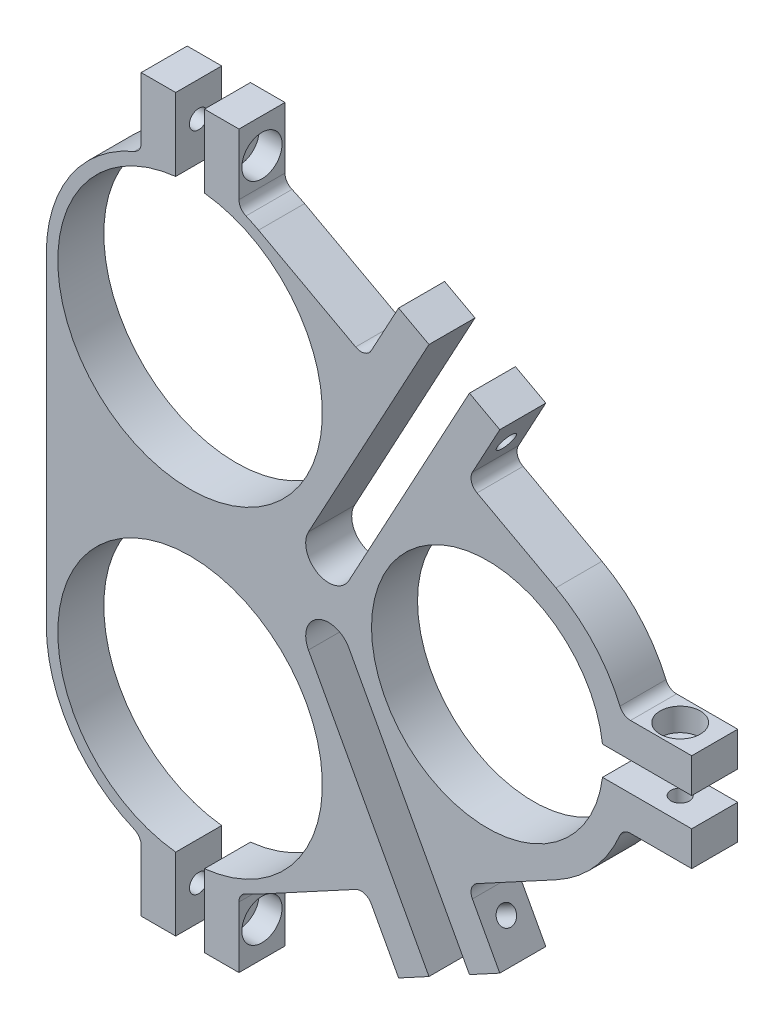
SolidWorks part; units mm, degrees
ref_plane "Front Plane" through (0, 0, 0) normal (0, 0, 1) x (1, 0, 0)
ref_plane "Top Plane" through (0, 0, 0) normal (0, 1, 0) x (1, 0, 0)
ref_plane "Right Plane" through (0, 0, 0) normal (1, 0, 0) x (0, 0, -1)
sketch "Sketch1" plane through (0, 0, 0) normal (0, 0, 1) x (1, 0, 0)
  line L0 (-39.6875, 88.9) -> (-39.6875, 0)
  line L1 (-39.6875, 44.45) -> (82.0822, 44.45) construction
  line L2 (18.8988, 123.7989) -> (48.4931, 107.7727)
  line L3 (3.9688, -36.2962) -> (3.9688, -56.3731)
  line L4 (0, 88.9) -> (0, 0) construction
  line L5 (-13.4938, -37.3231) -> (-13.4938, -56.3731)
  line L6 (3.9688, -56.3731) -> (13.4938, -56.3731)
  line L7 (-3.9688, -56.3731) -> (-13.4938, -56.3731)
  line L8 (13.4938, -37.3231) -> (13.4938, -56.3731)
  line L9 (-3.9687, -36.2962) -> (-3.9688, -56.3731)
  line L10 (18.8988, -34.8989) -> (48.4931, -18.8727)
  line L11 (13.4938, 126.2231) -> (13.4938, 145.2731)
  line L12 (-3.9688, 145.2731) -> (-13.4938, 145.2731)
  line L13 (3.9688, 145.2731) -> (13.4938, 145.2731)
  line L14 (3.9688, 145.2731) -> (3.9688, 125.1962)
  line L15 (-13.4938, 126.2231) -> (-13.4938, 145.2731)
  line L16 (56.8688, 103.237) -> (68.0364, 97.1894) construction
  line L17 (56.8688, 103.237) -> (32.6783, 58.5664)
  line L18 (-3.9688, 145.2731) -> (-3.9688, 125.1962)
  line L19 (68.0364, 97.1894) -> (43.846, 52.5188)
  line L20 (32.6783, 58.5664) -> (43.846, 52.5188) construction
  line L21 (56.8688, -14.337) -> (32.6783, 30.3336)
  line L22 (56.8688, 103.237) -> (65.9402, 119.9885)
  line L23 (3.9688, 145.2731) -> (-3.9688, 145.2731) construction
  line L24 (48.4931, 107.7727) -> (57.5645, 124.5242)
  line L25 (3.9688, -56.3731) -> (-3.9688, -56.3731) construction
  line L26 (65.9402, 119.9885) -> (57.5645, 124.5242)
  line L27 (38.2622, 55.5426) -> (62.4526, 100.2132) construction
  line L28 (68.0364, 97.1894) -> (77.1079, 113.9408)
  line L29 (77.1079, 113.9408) -> (85.4836, 109.4051)
  line L30 (76.4122, 92.6537) -> (85.4836, 109.4051)
  line L31 (76.4122, 92.6537) -> (100.981, 79.3489)
  line L32 (68.0364, -8.2894) -> (43.846, 36.3812)
  line L33 (76.4122, -3.7537) -> (85.4836, -20.5051)
  line L34 (77.1079, -25.0408) -> (85.4836, -20.5051)
  line L35 (68.0364, -8.2894) -> (77.1079, -25.0408)
  line L36 (56.8688, -14.337) -> (65.9402, -31.0885)
  line L37 (65.9402, -31.0885) -> (57.5645, -35.6242)
  line L38 (48.4931, -18.8727) -> (57.5645, -35.6242)
  line L39 (38.2622, 33.3574) -> (62.4526, -11.3132) construction
  line L40 (56.8688, -14.337) -> (68.0364, -8.2894) construction
  line L41 (76.4122, -3.7537) -> (100.981, 9.5511)
  line L42 (113.8392, 48.4187) -> (138.4553, 48.4187)
  line L43 (138.4553, 48.4187) -> (138.4553, 57.9437)
  line L44 (138.4553, 57.9437) -> (119.4053, 57.9437)
  line L45 (113.8392, 40.4812) -> (138.4553, 40.4812)
  line L46 (138.4553, 40.4812) -> (138.4553, 30.9563)
  line L47 (138.4553, 30.9563) -> (119.4053, 30.9562)
  arc A0 (3.9688, -36.2962) -> (-3.9687, -36.2962) centre (0, 0) ccw
  arc A1 (-3.9688, 125.1962) -> (3.9688, 125.1962) centre (0, 88.9) ccw
  arc A2 (13.4938, 126.2231) -> (18.8988, 123.7989) centre (0, 88.9) cw
  arc A3 (-39.6875, 0) -> (-13.4938, -37.3231) centre (0, 0) ccw
  arc A4 (113.8392, 48.4187) -> (113.8392, 40.4812) centre (82.0822, 44.45) ccw
  arc A5 (13.4938, -37.3231) -> (18.8988, -34.8989) centre (0, 0) ccw
  arc A6 (-39.6875, 88.9) -> (-13.4938, 126.2231) centre (0, 88.9) cw
  arc A7 (119.4053, 57.9437) -> (119.4053, 30.9562) centre (82.0822, 44.45) ccw construction
  circle A8 centre (0, 0) radius 36.5125 construction
  circle A9 centre (0, 88.9) radius 36.5125 construction
  circle A10 centre (0, 0) radius 39.6875 construction
  circle A11 centre (82.0822, 44.45) radius 36.5125 construction
  circle A12 centre (0, 88.9) radius 39.6875 construction
  arc A13 (100.981, 79.3489) -> (119.4053, 57.9437) centre (82.0822, 44.45) cw
  circle A14 centre (38.2622, 55.5426) radius 6.35 construction
  arc A15 (32.6783, 58.5664) -> (43.846, 52.5188) centre (38.2622, 55.5426) ccw
  circle A16 centre (38.2622, 33.3574) radius 6.35 construction
  arc A17 (32.6783, 30.3336) -> (43.846, 36.3812) centre (38.2622, 33.3574) cw
  arc A18 (119.4053, 30.9562) -> (100.981, 9.5511) centre (82.0822, 44.45) cw
  point P14 (0, 36.5125)
  dimension "D2" = 64.008
  dimension "D4" = 73.025
  dimension "D5" = 73.025
  dimension "D7" = 79.375
  dimension "D9" = 79.375
  dimension "D10" = 73.025
  dimension "D11" = 12.7
  dimension "D1" = 7.9375
  dimension "D3" = 88.9
  dimension "D6" = 9.525
  dimension "D8" = 19.05
  dimension "D12" = 93.345
  dimension "D13" = 43.18
  dimension "D14" = 50.8
  dimension "D15" = 19.05
  dimension "D16" = 9.525
  dimension "D17" = 9.525
  dimension "D18" = 7.9375
  dimension "D19" = 19.05
extrude "Extrude1" add sketch "Sketch1" along normal mid plane 12.7
hole_wizard "CBORE for 1/4 Socket Head Cap Screw1" positions "Sketch3" profile "Sketch2" counterbore size "1/4" standard "Ansi Inch" end condition up to next
sketch "Sketch3" plane through (13.4938, 0, 0) normal (1, 0, 0) x (0, 0, -1)
  line L0 (6.35, 145.2731) -> (-6.35, 126.2231) construction
  point P0 (0, 135.7481)
sketch "Sketch2" plane through (13.4938, 135.7481, 0) normal (0, 1, 0) x (0, 0, -1)
  line L0 (0, 0) -> (0, 9.525)
  line L1 (0, 9.525) -> (3.3782, 9.525)
  line L3 (3.3782, 9.525) -> (3.3782, 6.35)
  line L4 (3.3782, 6.35) -> (5.5562, 6.35)
  line L5 (5.5562, 6.35) -> (5.5562, 0)
  line L7 (5.5562, 0) -> (0, 0)
  line L11 (0, -6.35) -> (0, 107.95) construction
  dimension "Thru Hole Dia." = 6.7564
  dimension "Thru Hole Depth" = 9.525
  dimension "C'Bore Dia." = 11.1125
  dimension "C'Bore Depth" = 6.35
hole_wizard "1/4-20 Tapped Hole1" positions "Sketch5" profile "Sketch4" tap size "1/4-20" standard "Ansi Inch" end condition through all
sketch "Sketch5" plane through (-3.9688, 0, 0) normal (1, 0, 0) x (0, 0, -1)
  point P0 (0, 135.7481)
sketch "Sketch4" plane through (-3.9688, 135.7481, 0) normal (0, 1, 0) x (0, 0, -1)
  line L0 (0, 0) -> (0, 35.7188)
  line L1 (0, 35.7188) -> (2.5527, 35.7188)
  line L2 (2.5527, 35.7188) -> (2.5527, 0)
  line L5 (2.5527, 0) -> (0, 0)
  line L11 (0, -6.35) -> (0, 107.95) construction
  dimension "Thru Tap Drill Dia." = 5.1054
  dimension "Thru Tap Drill Depth" = 35.7188
cosmetic thread "Hole Thread1" parameters "D2"=6.35
hole_wizard "CBORE for 1/4 Socket Head Cap Screw3" positions "Sketch16" profile "Sketch17" counterbore size "1/4" standard "Ansi Inch" end condition up to next
sketch "Sketch16" plane through (13.4938, 0, 0) normal (1, 0, 0) x (0, 0, -1)
  line L0 (6.35, -37.3231) -> (-6.35, -56.3731) construction
  point P0 (0, -46.8481)
sketch "Sketch17" plane through (13.4938, -46.8481, 0) normal (0, 1, 0) x (0, 0, -1)
  line L0 (0, 0) -> (0, 9.525)
  line L1 (0, 9.525) -> (3.3782, 9.525)
  line L3 (3.3782, 9.525) -> (3.3782, 6.35)
  line L4 (3.3782, 6.35) -> (5.5562, 6.35)
  line L5 (5.5562, 6.35) -> (5.5562, 0)
  line L7 (5.5562, 0) -> (0, 0)
  line L11 (0, -6.35) -> (0, 107.95) construction
  dimension "Thru Hole Dia." = 6.7564
  dimension "Thru Hole Depth" = 9.525
  dimension "C'Bore Dia." = 11.1125
  dimension "C'Bore Depth" = 6.35
hole_wizard "1/4-20 Tapped Hole4" positions "Sketch19" profile "Sketch21" tap size "1/4-20" standard "Ansi Inch" end condition through all
sketch "Sketch19" plane through (-3.9687, 0, 0) normal (1, 0, 0) x (0, 0, -1)
  point P0 (0, -46.8481)
sketch "Sketch21" plane through (-3.9687, -46.8481, 0) normal (0, 1, 0) x (0, 0, -1)
  line L0 (0, 0) -> (0, 35.7188)
  line L1 (0, 35.7188) -> (2.5527, 35.7188)
  line L2 (2.5527, 35.7188) -> (2.5527, 0)
  line L5 (2.5527, 0) -> (0, 0)
  line L11 (0, -6.35) -> (0, 107.95) construction
  dimension "Thru Tap Drill Dia." = 5.1054
  dimension "Thru Tap Drill Depth" = 35.7188
cosmetic thread "Hole Thread4" parameters "D2"=6.35
sketch "Sketch29" plane through (20.2879, -10.9865, 0) normal (0.8793, -0.4762, 0) x (0, 0, -1)
  line L0 (6.35, 136.911) -> (-6.35, 117.861) construction
hole_wizard "Tap Drill for 1/4-20 Tap1" positions "Sketch30" profile "Sketch31" hole size "1/4-20" standard "ANSI Inch" end condition up to next
sketch "Sketch30" plane through (20.2879, -10.9865, 0) normal (0.8793, -0.4762, 0) x (0, 0, -1)
  line L0 (6.35, 136.911) -> (-6.35, 117.861) construction
  point P0 (0, 127.386)
sketch "Sketch31" plane through (80.9479, 101.0294, 0) normal (0, 0, 1) x (0.4762, 0.8793, 0)
  line L0 (0, 0) -> (0, 9.525)
  line L1 (0, 9.525) -> (2.5527, 9.525)
  line L2 (2.5527, 9.525) -> (2.5527, 0)
  line L5 (2.5527, 0) -> (0, 0)
  line L11 (0, -6.35) -> (0, 107.95) construction
  dimension "Thru Hole Dia." = 5.1054
  dimension "Thru Hole Depth" = 9.525
sketch "Sketch41" plane through (0, 57.9437, 0) normal (0, 1, 0) x (1, 0, 0)
  line L0 (138.4553, 6.35) -> (119.4053, -6.35) construction
hole_wizard "CBORE for 1/4 Socket Head Cap Screw6" positions "Sketch42" profile "Sketch43" counterbore size "1/4" standard "ANSI Inch" end condition up to next
sketch "Sketch42" plane through (0, 57.9437, 0) normal (0, 1, 0) x (1, 0, 0)
  line L0 (138.4553, 6.35) -> (119.4053, -6.35) construction
  point P0 (128.9303, 0)
sketch "Sketch43" plane through (128.9303, 57.9437, 0) normal (1, 0, 0) x (0, 0, 1)
  line L0 (0, 0) -> (0, 9.525)
  line L1 (0, 9.525) -> (3.3782, 9.525)
  line L3 (3.3782, 9.525) -> (3.3782, 6.35)
  line L4 (3.3782, 6.35) -> (5.5562, 6.35)
  line L5 (5.5562, 6.35) -> (5.5563, 0)
  line L7 (5.5563, 0) -> (0, 0)
  line L11 (0, -6.35) -> (0, 107.95) construction
  dimension "Thru Hole Dia." = 6.7564
  dimension "Thru Hole Depth" = 9.525
  dimension "C'Bore Dia." = 11.1125
  dimension "C'Bore Depth" = 6.35
hole_wizard "1/4-20 Tapped Hole7" positions "Sketch44" profile "Sketch45" tap size "1/4-20" standard "ANSI Inch" end condition up to next
sketch "Sketch44" plane through (0, 40.4813, 0) normal (0, 1, 0) x (1, 0, 0)
  line L0 (138.4553, 6.35) -> (119.4053, -6.35) construction
  point P0 (128.9303, 0)
sketch "Sketch45" plane through (128.9303, 40.4813, 0) normal (1, 0, 0) x (0, 0, 1)
  line L0 (0, 0) -> (0, 9.525)
  line L1 (0, 9.525) -> (2.5527, 9.525)
  line L2 (2.5527, 9.525) -> (2.5527, 0)
  line L5 (2.5527, 0) -> (0, 0)
  line L11 (0, -6.35) -> (0, 107.95) construction
  dimension "Thru Tap Drill Dia." = 5.1054
  dimension "Thru Tap Drill Depth" = 9.525
cosmetic thread "Hole Thread7" parameters "D2"=6.35
sketch "Sketch46" plane through (57.5134, 31.1452, 0) normal (0.8793, 0.4762, 0) x (0, 0, -1)
  line L0 (-6.35, -39.6875) -> (6.35, -58.7375) construction
hole_wizard "Tap Drill for 1/4-20 Tap2" positions "Sketch47" profile "Sketch48" hole size "1/4-20" standard "ANSI Inch" end condition up to next
sketch "Sketch47" plane through (57.5134, 31.1452, 0) normal (0.8793, 0.4762, 0) x (0, 0, -1)
  line L0 (-6.35, -39.6875) -> (6.35, -58.7375) construction
  point P0 (0, -49.2125)
sketch "Sketch48" plane through (80.9479, -12.1294, 0) normal (0, 0, 1) x (-0.4762, 0.8793, 0)
  line L0 (0, 0) -> (0, 9.525)
  line L1 (0, 9.525) -> (2.5527, 9.525)
  line L2 (2.5527, 9.525) -> (2.5527, 0)
  line L5 (2.5527, 0) -> (0, 0)
  line L11 (0, -6.35) -> (0, 107.95) construction
  dimension "Thru Hole Dia." = 5.1054
  dimension "Thru Hole Depth" = 9.525
fillet "Fillet1" radius 3.175 10 edges at (13.4938, 126.2231, 0) (-13.4938, 126.2231, 0) (-13.4938, -37.3231, 0) (13.4938, -37.3231, 0) (48.4931, 107.7727, 0) (76.4122, 92.6537, 0) (119.4053, 30.9562, 0) (119.4053, 57.9437, 0) (48.4931, -18.8727, 0) (76.4122, -3.7537, 0)
